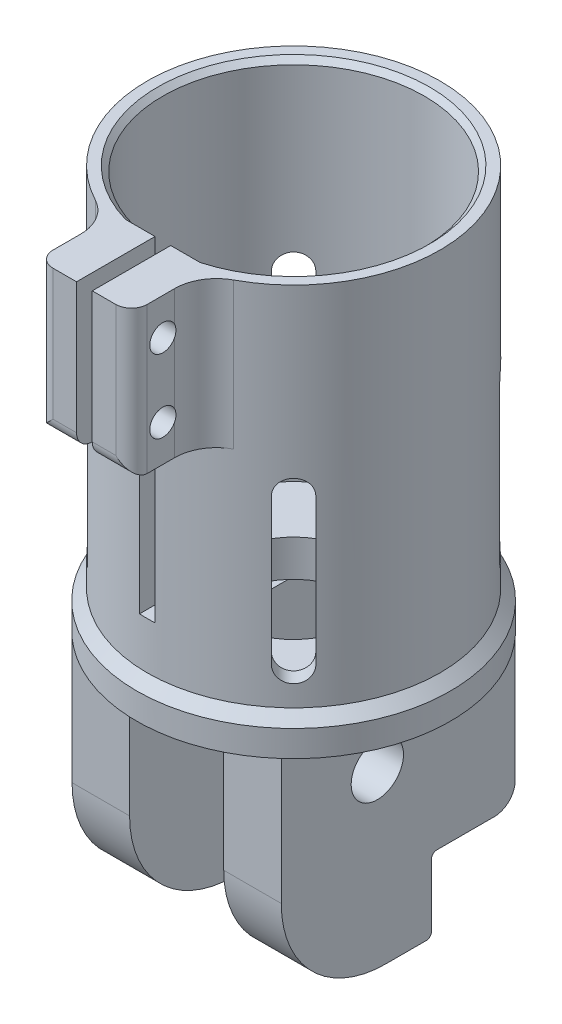
SolidWorks part; units mm, degrees
ref_plane "Front" through (0, 0, 0) normal (0, 0, 1) x (1, 0, 0)
ref_plane "Top" through (0, 0, 0) normal (0, 1, 0) x (1, 0, 0)
ref_plane "Right" through (0, 0, 0) normal (1, 0, 0) x (0, 0, -1)
sketch "Esquisse1" plane through (0, 0, 0) normal (0, 0, 1) x (1, 0, 0)
  line L0 (0, 0) -> (0, 39.8665) construction
  line L1 (-6, 0) -> (-15, 0)
  line L2 (-15, 0) -> (-15, 3.5)
  line L3 (-15, 3.5) -> (-14, 3.5)
  line L4 (-14, 3.5) -> (-14, 38.5)
  line L5 (-14, 38.5) -> (-12.5, 38.5)
  line L6 (-12.5, 38.5) -> (-12.5, 3.5)
  line L7 (-12.5, 3.5) -> (-6, 3.5)
  line L8 (-6, 3.5) -> (-6, 0)
  point P11 (0, 0)
  point P13 (-8.4426, 0)
  dimension "D1" = 25
  dimension "D2" = 28
  dimension "D3" = 35
  dimension "D4" = 3.5
  dimension "D5" = 30
  dimension "D6" = 12
revolve "Révolution1" add sketch "Esquisse1" angle 360 about L0
chamfer "Chanfrein1" distance 1 angle 45 1 edges at (0, 3.5, -15)
sketch "Esquisse2" plane through (0, 0, 0) normal (0, -1, 0) x (1, 0, 0)
  line L0 (0, 0) -> (0, 16.0415) construction
  line L1 (-10, 11.1803) -> (-4.5, 11.1803)
  line L2 (-10, 11.1803) -> (-10, -11.1803)
  line L3 (-10, -11.1803) -> (-4.5, -11.1803)
  line L4 (-4.5, 11.1803) -> (-4.5, -11.1803)
  line L5 (4.5, 11.1803) -> (4.5, -11.1803)
  line L6 (10, -11.1803) -> (4.5, -11.1803)
  line L7 (10, 11.1803) -> (10, -11.1803)
  line L8 (10, 11.1803) -> (4.5, 11.1803)
  circle A0 centre (0, 0) radius 15 construction
  dimension "D1" = 20
  dimension "D2" = 9
extrude "Boss.-Extru.1" add sketch "Esquisse2" along normal blind 22
fillet "Congé1" radius 10 2 edges at (-7.25, -22, 11.1803) (7.25, -22, 11.1803)
sketch "Esquisse3" plane through (-10, 0, 0) normal (-1, 0, 0) x (0, 0, 1)
  line L0 (-11.1803, 0) -> (11.1803, 0) construction
  line L1 (-11.1803, -22) -> (-3.1803, -22)
  line L2 (-11.1803, -22) -> (-11.1803, -15)
  line L3 (-11.1803, -15) -> (-3.1803, -15)
  line L4 (-3.1803, -22) -> (-3.1803, -15)
  dimension "D1" = 15
  dimension "D2" = 8
extrude "Enlèv. mat.-Extru.1" cut sketch "Esquisse3" against normal through all
fillet "Congé2" radius 2 2 edges at (7.25, -15, -11.1803) (-7.25, -15, -11.1803)
fillet "Congé3" radius 0.5 4 edges at (7.25, -22, -3.1803) (-7.25, -22, -3.1803) (7.25, -15, -3.1803) (-7.25, -15, -3.1803)
sketch "Esquisse4" plane through (0, 0, 0) normal (1, 0, 0) x (0, 0, -1)
  line L0 (11.1803, 0) -> (-11.1803, 0) construction
  line L1 (-15, 2.5) -> (-15, 0) construction
  circle A0 centre (-2, -5.5) radius 2.5
  dimension "D1" = 5.5
  dimension "D3" = 5
  dimension "D2" = 13
extrude "Enlèv. mat.-Extru.2" cut sketch "Esquisse4" against normal through all both and the other way through all
chamfer "Chanfrein2" distance 0.5 angle 45 1 edges at (0, 38.5, -12.5)
sketch "Esquisse6" plane through (0, 0, 0) normal (1, 0, 0) x (0, 0, -1)
  line L0 (14, 38.5) -> (-14, 38.5) construction
  line L1 (-20, 38.5) -> (-12.5, 38.5)
  line L2 (-20, 38.5) -> (-20, 24.5)
  line L3 (-20, 24.5) -> (-12.5, 24.5)
  line L4 (-12.5, 38.5) -> (-12.5, 24.5)
  point P6 (0, 0)
  point P7 (10.9998, 38.5)
  point P9 (-11.3736, 38.5)
  dimension "D1" = 12.5
  dimension "D2" = 14
  dimension "D3" = 7.5
extrude "Boss.-Extru.2" add sketch "Esquisse6" along normal mid plane 9
fillet "Congé4" radius 4 2 edges at (4.5, 31.5, 13.2571) (-4.5, 31.5, 13.2571)
fillet "Congé5" radius 1.5 3 edges at (-4.5, 31.5, 20) (0, 24.5, 20) (4.5, 31.5, 20)
sketch "Esquisse5" plane through (0, 0, 0) normal (0, 0, 1) x (1, 0, 0)
  line L0 (14, 38.5) -> (-14, 38.5) construction
  line L1 (-0.75, 69) -> (0.75, 69)
  line L2 (-0.75, 69) -> (-0.75, 8)
  line L3 (-0.75, 8) -> (0.75, 8)
  line L4 (0.75, 69) -> (0.75, 8)
  line L5 (-0.75, 69) -> (0.75, 8) construction
  line L6 (-0.75, 8) -> (0.75, 69) construction
  line L7 (-10, 0) -> (10, 0) construction
  point P0 (0, 38.5)
  dimension "D1" = 8
  dimension "D2" = 1.5
extrude "Enlèv. mat.-Extru.3" cut sketch "Esquisse5" along normal through all
sketch "Esquisse7" plane through (0, 0, 0) normal (1, 0, 0) x (0, 0, -1)
  line L1 (-15.8666, 38.5) -> (-18.5, 38.5) construction
  circle A0 centre (-17, 28) radius 1.25
  circle A1 centre (-17, 35) radius 1.25
  point P4 (0, 0)
  point P5 (-16.8805, 27.5497)
  point P8 (-19.7362, 42)
  point P9 (-17.3695, 35)
  dimension "D1" = 2.5
  dimension "D2" = 7
  dimension "D3" = 3.5
  dimension "D4" = 17
extrude "Enlèv. mat.-Extru.4" cut sketch "Esquisse7" against normal through all both and the other way through all
ref_plane "Plan1" through (9.8995, 0, -9.8995) normal (0.7071, 0, -0.7071) x (0, -1, 0)
sketch "Esquisse8" plane through (9.8995, 0, -9.8995) normal (0.7071, 0, -0.7071) x (0, -1, 0)
  line L0 (-7, 0) -> (-21, 0) construction
  line L1 (-7, -1.5) -> (-21, -1.5)
  line L2 (-7, 1.5) -> (-21, 1.5)
  line L3 (0, 0.8346) -> (0, 14.9768) construction
  arc A0 (-7, -1.5) -> (-7, 1.5) centre (-7, 0) ccw
  arc A1 (-21, 1.5) -> (-21, -1.5) centre (-21, 0) ccw
  point P3 (-14, 0)
  point P8 (-22.5, 0)
  point P9 (-5.5, 0)
  dimension "D1" = 3
  dimension "D2" = 17
  dimension "D3" = 5.5
extrude "Enlèv. mat.-Extru.5" cut sketch "Esquisse8" against normal up to next
pattern_circular "Répétition circulaire1" count 4 over 360 about axis through (0, 0, 0) along (0, -1, 0) of "Enlèv. mat.-Extru.5"
